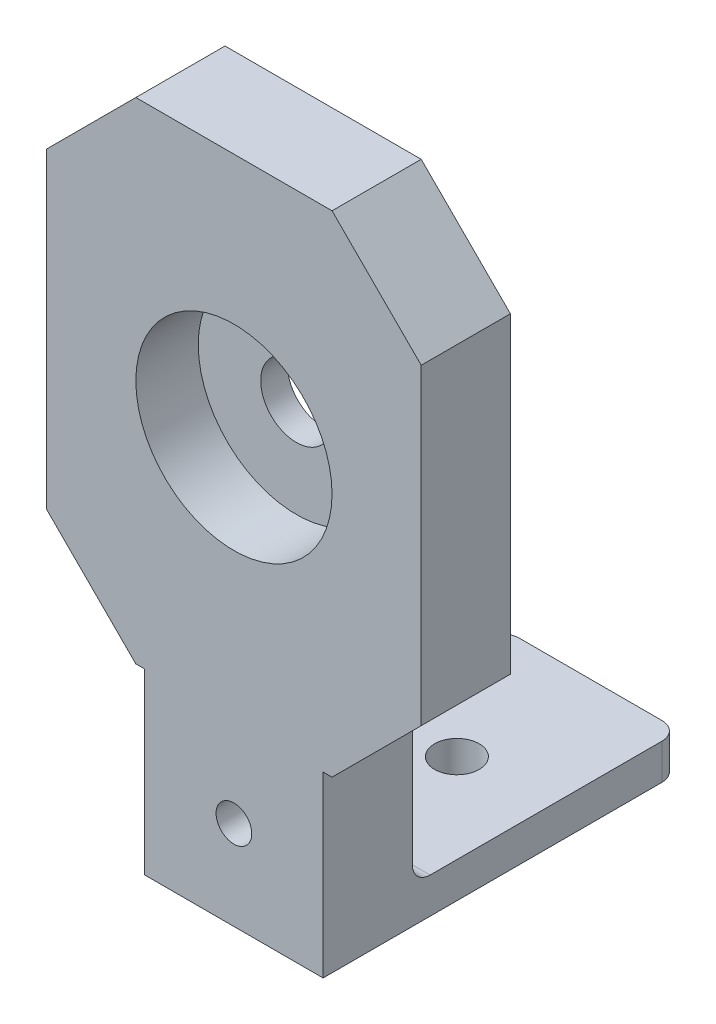
SolidWorks part; units mm, degrees
material "PLA"
ref_plane "Piano frontale" through (0, 0, 0) normal (0, 0, 1) x (1, 0, 0)
ref_plane "Piano superiore" through (0, 0, 0) normal (0, 1, 0) x (1, 0, 0)
ref_plane "Piano destro" through (0, 0, 0) normal (1, 0, 0) x (0, 0, -1)
sketch "Schizzo1" plane through (0, 0, 0) normal (0, 0, 1) x (1, 0, 0)
  line L0 (0, 0) -> (0, -47.5) construction
  line L1 (-10, -47.5) -> (10, -47.5)
  line L2 (-21, -27.5) -> (-21, 27.5)
  line L3 (-21, 27.5) -> (21, 27.5)
  line L4 (21, -27.5) -> (21, 27.5)
  line L5 (-21, -27.5) -> (21, 27.5) construction
  line L6 (-21, 27.5) -> (21, -27.5) construction
  line L7 (-10, -47.5) -> (-10, -27.5)
  line L8 (-10, -27.5) -> (-21, -27.5)
  line L9 (10, -47.5) -> (10, -27.5)
  line L10 (10, -27.5) -> (21, -27.5)
  point P0 (0, 0)
  dimension "D1" = 42
  dimension "D3" = 20
  dimension "D4" = 10
  dimension "D5" = 55
extrude "Estrusione-Estrusione1" add sketch "Schizzo1" along normal blind 10
sketch "Schizzo6" plane through (0, 0, 10) normal (0, 0, 1) x (1, 0, 0)
  line L0 (-10, -47.5) -> (10, -47.5) construction
  line L1 (21, 27.5) -> (-21, 27.5) construction
  circle A0 centre (0, 0) radius 11
  dimension "D1" = 22
  dimension "D2" = 47.5
extrude "Taglio-Estrusione4" cut sketch "Schizzo6" against normal blind 7
sketch "Schizzo7" plane through (0, 0, 3) normal (0, 0, 1) x (1, 0, 0)
  circle A0 centre (0, 0) radius 4
  dimension "D1" = 8
extrude "Taglio-Estrusione5" cut sketch "Schizzo7" against normal through all
chamfer "Smusso2" distance 10 angle 45 4 edges at (-21, -27.5, 5) (21, -27.5, 5) (21, 27.5, 5) (-21, 27.5, 5)
sketch "Schizzo8" plane through (0, 0, 0) normal (0, 0, -1) x (-1, 0, 0)
  line L0 (10, -27.5) -> (10, -47.5) construction
  line L1 (-10, -47.5) -> (10, -47.5)
  line L2 (-10, -47.5) -> (-10, -43.5)
  line L3 (-10, -43.5) -> (10, -43.5)
  line L4 (10, -47.5) -> (10, -43.5)
  dimension "D1" = 4
extrude "Estrusione-Estrusione3" add sketch "Schizzo8" along normal blind 30
sketch "Schizzo9" plane through (0, -43.5, 0) normal (0, 1, 0) x (1, 0, 0)
  line L0 (0, 30) -> (0, 0) construction
  line L1 (-10, 30) -> (10, 30) construction
  line L2 (11, 0) -> (-11, 0) construction
  circle A0 centre (0, 15) radius 2.5
  dimension "D1" = 5
  dimension "D3" = 15
extrude "Taglio-Estrusione6" cut sketch "Schizzo9" against normal blind 35
fillet "Raccordo1" radius 2 3 edges at (0, -43.5, 0) (-10, -45.5, -30) (10, -45.5, -30)
sketch "Schizzo10" plane through (0, 0, 0) normal (0, 0, -1) x (-1, 0, 0)
  line L0 (-8, -47.5) -> (8, -47.5) construction
  circle A0 centre (0, -37.5) radius 2
  dimension "D2" = 4
  dimension "D1" = 10
extrude "Taglio-Estrusione7" cut sketch "Schizzo10" against normal blind 10
